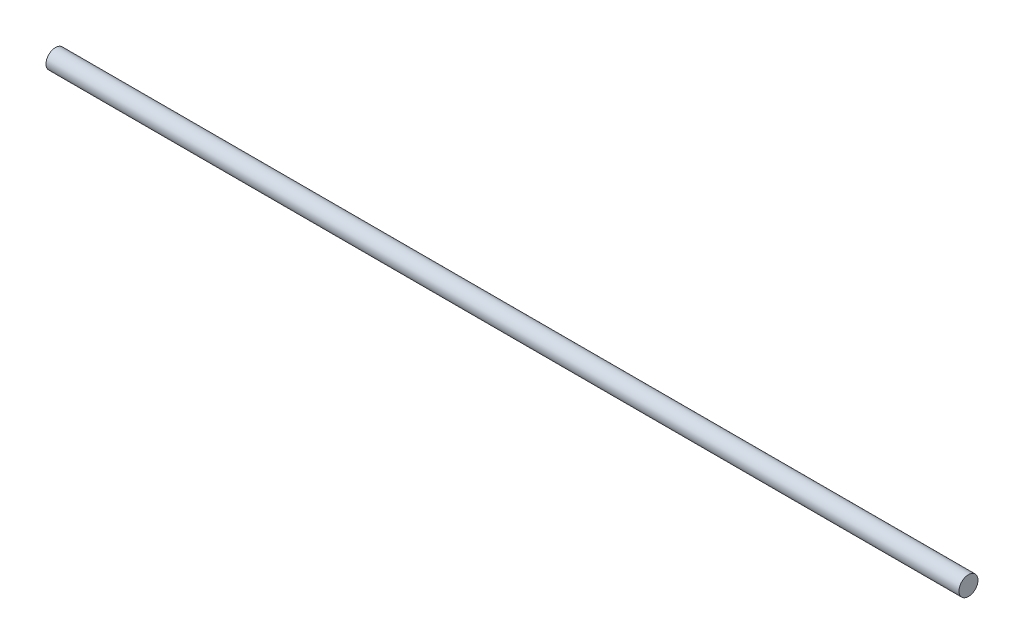
SolidWorks part; units mm, degrees
ref_plane "Front Plane" through (0, 0, 0) normal (0, 0, 1) x (1, 0, 0)
ref_plane "Top Plane" through (0, 0, 0) normal (0, 1, 0) x (1, 0, 0)
ref_plane "Right Plane" through (0, 0, 0) normal (1, 0, 0) x (0, 0, -1)
sketch "Sketch1" plane through (0, 0, 0) normal (1, 0, 0) x (0, 0, -1)
  circle A0 centre (0, 0) radius 1.505
  dimension "D1" = 3.0099
extrude "Boss-Extrude1" add sketch "Sketch1" along normal mid plane 144.6022
